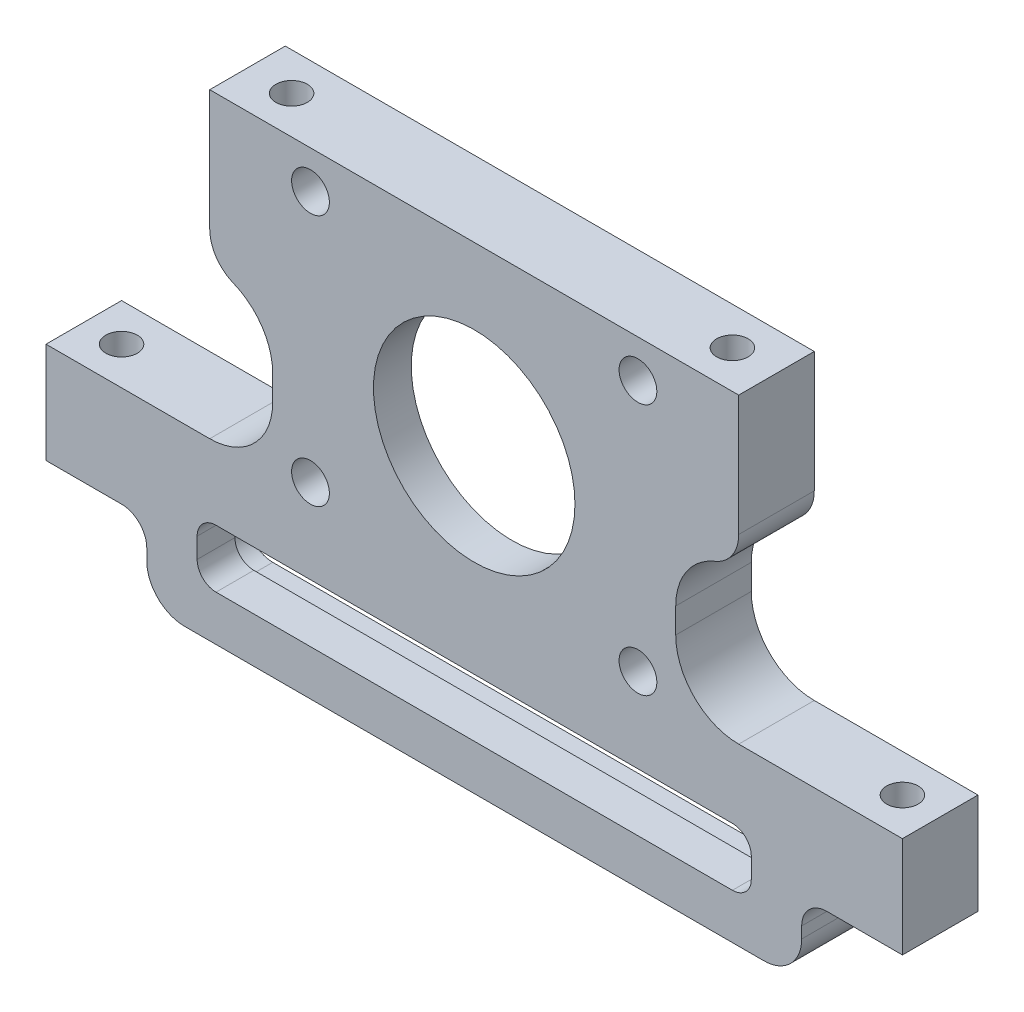
SolidWorks part; units mm, degrees
material "1060 Alloy"
ref_plane "Front Plane" through (0, 0, 0) normal (0, 0, 1) x (1, 0, 0)
ref_plane "Top Plane" through (0, 0, 0) normal (0, 1, 0) x (1, 0, 0)
ref_plane "Right Plane" through (0, 0, 0) normal (1, 0, 0) x (0, 0, -1)
sketch "Sketch1" plane through (0, 0, 0) normal (0, 0, 1) x (1, 0, 0)
  line L0 (18, 32) -> (50, 32)
  line L1 (8, 0) -> (8, -5.9)
  line L2 (50, 32) -> (50, 8)
  line L3 (18, 32) -> (18, 8)
  line L4 (12, 2.3) -> (56, 2.3)
  line L5 (12, 2.3) -> (12, -2.3)
  line L6 (12, -2.3) -> (56, -2.3)
  line L7 (56, 2.3) -> (56, -2.3)
  line L8 (8, -5.9) -> (60, -5.9)
  line L9 (60, -5.9) -> (60, 0)
  line L10 (8, 0) -> (0, 0)
  line L11 (0, 0) -> (0, 8)
  line L12 (0, 8) -> (18, 8)
  line L13 (50, 8) -> (68, 8)
  line L14 (68, 8) -> (68, 0)
  line L15 (68, 0) -> (60, 0)
  circle A0 centre (34, 18) radius 8
  dimension "D4" = 16
  dimension "D1" = 4.6
  dimension "D2" = 44
  dimension "D3" = 3.6
  dimension "D5" = 4
  dimension "D6" = 4
  dimension "D7" = 32
  dimension "D8" = 16
  dimension "D9" = 18
  dimension "D10" = 8
  dimension "D11" = 15.7
  dimension "D12" = 8
  dimension "D14" = 32
extrude "Boss-Extrude1" add sketch "Sketch1" along normal blind 6
sketch "Sketch3" plane through (0, 0, 0) normal (0, 0, -1) x (-1, 0, 0)
  circle A0 centre (-34, 18) radius 13
  dimension "D1" = 26
extrude "Cut-Extrude2" cut sketch "Sketch3" against normal offset from surface (3 mm away) 3 up to face at (34, 0, 6)
hole_wizard "Tap Drill for M3 Tap2" positions "Sketch5" profile "Sketch4" hole size "M3" standard "ISO"
sketch "Sketch5" plane through (38.1016, 0, -22.7468) normal (0, -1, 0) x (-1, 0, 0)
  line L3 (-29.8984, -28.7468) -> (-29.8984, -22.7468) construction
  line L4 (38.1016, -28.7468) -> (38.1016, -22.7468) construction
  line L5 (-21.8984, -28.7468) -> (-29.8984, -28.7468) construction
  point P0 (35.1016, -25.7468)
  point P2 (-26.8984, -25.7468)
  dimension "D1" = 3
  dimension "D2" = 3
  dimension "D3" = 3
sketch "Sketch4" plane through (3, 0, 3) normal (1, 0, 0) x (0, 0, -1)
  line L0 (0, 0) -> (0, 8.7511)
  line L1 (0, 8.7511) -> (1.25, 8)
  line L2 (1.25, 8) -> (1.25, 0)
  line L5 (1.25, 0) -> (0, 0)
  line L10 (0, 8.7511) -> (-1.25, 8) construction
  line L11 (0, -6.35) -> (0, 107.95) construction
  dimension "Hole Dia." = 2.5
  dimension "Hole Depth" = 8
  dimension "Drill Angle" = 118
sketch "Sketch10" plane through (0, 0, 0) normal (0, 0, -1) x (-1, 0, 0)
  line L0 (-56, -2.3) -> (-56, 2.3) construction
  line L1 (-58, 4) -> (-10, 4)
  line L2 (-58, 4) -> (-58, -4)
  line L3 (-58, -4) -> (-10, -4)
  line L4 (-10, 4) -> (-10, -4)
  line L8 (-56, 2.3) -> (-12, 2.3) construction
  line L9 (-12, 2.3) -> (-12, -2.3) construction
  dimension "D1" = 8
  dimension "D2" = 1.7
  dimension "D3" = 2
  dimension "D4" = 2
extrude "Cut-Extrude5" cut sketch "Sketch10" against normal blind 3
sketch "Sketch11" plane through (0, 0, 6) normal (0, 0, 1) x (1, 0, 0)
  line L1 (18, 32) -> (13, 32)
  line L2 (18, 32) -> (18, 20)
  line L3 (18, 20) -> (13, 20)
  line L4 (13, 32) -> (13, 20)
  line L6 (50, 32) -> (55, 32)
  line L7 (50, 32) -> (50, 20)
  line L8 (50, 20) -> (55, 20)
  line L9 (55, 32) -> (55, 20)
  line L10 (18, 8) -> (0, 8) construction
  dimension "D1" = 42
  dimension "D2" = 12
extrude "Boss-Extrude2" add sketch "Sketch11" against normal up to surface (6 mm away) up to face at (34, 0, 0)
fillet "Fillet6" radius 1.5 4 edges at (56, 2.3, 4.5) (56, -2.3, 4.5) (12, -2.3, 4.5) (12, 2.3, 4.5)
fillet "Fillet1" radius 2 4 edges at (10, -4, 1.5) (10, 4, 1.5) (58, -4, 1.5) (58, 4, 1.5)
hole_wizard "M3x0.5 Tapped Hole1" positions "3DSketch1" profile "Sketch13" tap size "M3x0.5" standard "ANSI Metric"
sketch3d "3DSketch1"
  line L1 (13, 32, 0) -> (55, 32, 0) construction
  line L2 (13, 32, 0) -> (55, 32, 0) construction
  point P0 (51.5, 32, 3)
  point P2 (16.5, 32, 3)
  dimension "D1" = 35
  dimension "D2" = 3
  dimension "D3" = 3
  dimension "D4" = 1.5
sketch "Sketch13" plane through (51.5, 32, 3) normal (1, 0, 0) x (0, 0, 1)
  line L0 (0, 0) -> (0, 10.2511)
  line L1 (0, 10.2511) -> (1.25, 9.5)
  line L2 (1.25, 9.5) -> (1.25, 0)
  line L5 (1.25, 0) -> (0, 0)
  line L10 (0, 10.2511) -> (-1.25, 9.5) construction
  line L11 (0, -6.35) -> (0, 107.95) construction
  dimension "Tap Drill Dia." = 2.5
  dimension "Tap Drill Depth" = 9.5
  dimension "Drill Angle" = 118
cosmetic thread "Hole Thread1" parameters "D1"=8, "D2"=3
cosmetic thread "Hole Thread2" parameters "D1"=8, "D2"=3
fillet "Fillet3" radius 5 4 edges at (18, 20, 3) (18, 8, 3) (50, 8, 3) (50, 20, 3)
sketch "Sketch14" plane through (0, 0, 6) normal (0, 0, 1) x (1, 0, 0)
  line L0 (55, 32) -> (13, 32) construction
  line L1 (18, 32) -> (50, 32) construction
  line L2 (18, 32) -> (18, 6) construction
  line L3 (18, 6) -> (50, 6) construction
  line L4 (50, 32) -> (50, 6) construction
  line L5 (50, 13) -> (50, 15) construction
  line L6 (18, 15) -> (18, 13) construction
  circle A0 centre (21, 29) radius 1.5
  circle A1 centre (47, 29) radius 1.5
  circle A2 centre (21, 9) radius 1.5
  circle A3 centre (47, 9) radius 1.5
  dimension "D1" = 3
  dimension "D2" = 3
  dimension "D3" = 3
  dimension "D4" = 3
  dimension "D5" = 3
  dimension "D6" = 26
extrude "Cut-Extrude7" cut sketch "Sketch14" against normal through all
fillet "Fillet4" radius 2 2 edges at (8, 0, 3) (60, 0, 3)
fillet "Fillet5" radius 3 4 edges at (8, -5.9, 3) (60, -5.9, 3) (13, 20, 3) (55, 20, 3)
